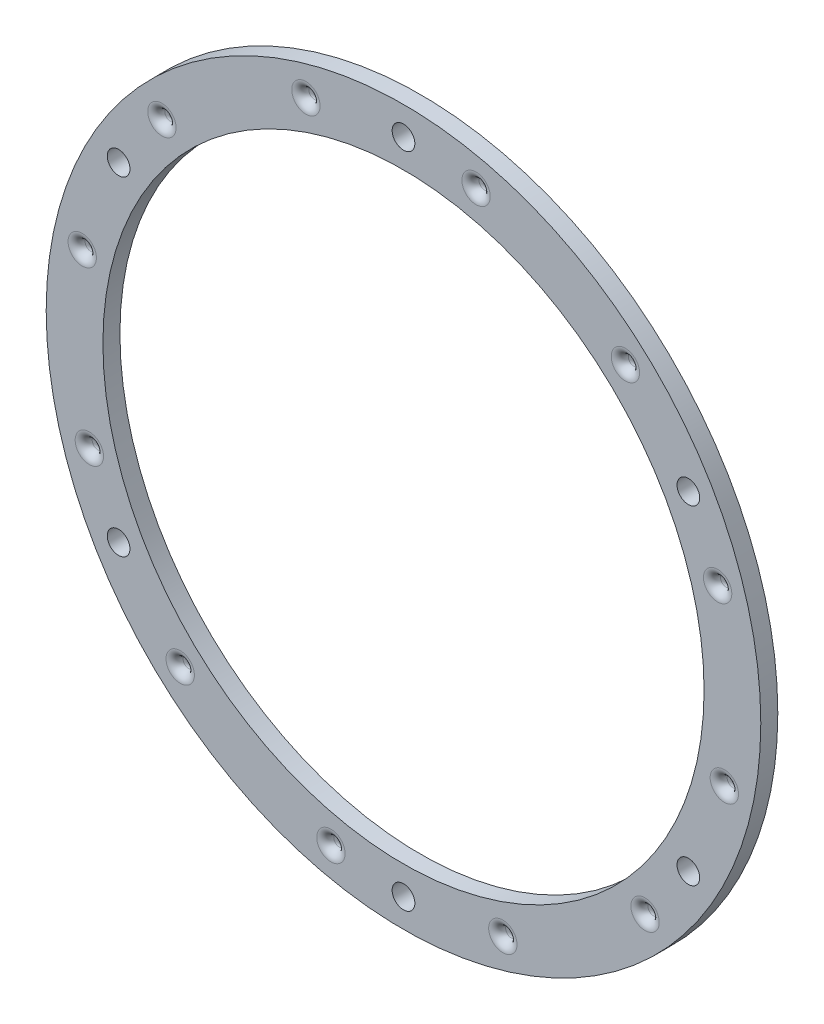
SolidWorks part; units mm, degrees
ref_plane "前视基准面" through (0, 0, 0) normal (0, 0, 1) x (1, 0, 0)
ref_plane "上视基准面" through (0, 0, 0) normal (0, 1, 0) x (1, 0, 0)
ref_plane "右视基准面" through (0, 0, 0) normal (1, 0, 0) x (0, 0, -1)
other "Configuration Table"
sketch "草图1" plane through (0, 0, 0) normal (0, 0, 1) x (1, 0, 0)
  line L0 (92.8146, -27.9977) -> (56.5708, -12.7963) construction
  line L1 (94.3787, 22.1606) -> (55.3899, 17.2035) construction
  line L2 (100.4589, 58) -> (0, 0) construction
  line L3 (70.654, 66.381) -> (39.1279, 42.8136) construction
  line L4 (33.6278, 38.6318) -> (56.5539, 56.0626) construction
  line L5 (27.9977, 92.8146) -> (12.7963, 56.5708) construction
  circle A0 centre (0, 0) radius 63
  circle A1 centre (0, 58) radius 2
  circle A22 centre (0, 0) radius 53
  circle A28 centre (50.2295, 29) radius 2
  circle A34 centre (50.2295, -29) radius 2
  circle A40 centre (0, -58) radius 2
  circle A46 centre (-50.2295, -29) radius 2
  circle A52 centre (-50.2295, 29) radius 2
  circle A58 centre (19.8372, 54.5022) radius 2 [skipped]
  circle A59 centre (37.2817, 44.4306) radius 2 [skipped]
  circle A60 centre (57.1188, 10.0716) radius 2 [skipped]
  circle A61 centre (57.1188, -10.0716) radius 2 [skipped]
  circle A62 centre (37.2817, -44.4306) radius 2 [skipped]
  circle A63 centre (19.8372, -54.5022) radius 2 [skipped]
  circle A64 centre (-19.8372, -54.5022) radius 2 [skipped]
  circle A65 centre (-37.2817, -44.4306) radius 2 [skipped]
  circle A66 centre (-57.1188, -10.0716) radius 2 [skipped]
  circle A67 centre (-57.1188, 10.0716) radius 2 [skipped]
  circle A68 centre (-37.2817, 44.4306) radius 2 [skipped]
  circle A69 centre (-19.8372, 54.5022) radius 2 [skipped]
  circle A70 centre (0, 0) radius 58 construction
  circle A71 centre (55.3899, 17.2035) radius 1
  circle A72 centre (56.5708, -12.7963) radius 1
  circle A73 centre (12.7963, 56.5708) radius 1
  circle A74 centre (39.1279, 42.8136) radius 1
  circle A75 centre (-39.3673, -42.5936) radius 1
  circle A76 centre (-12.7963, -56.5708) radius 1
  circle A77 centre (17.5137, -55.2926) radius 1
  circle A78 centre (42.5936, -39.3673) radius 1
  circle A79 centre (-17.2035, 55.3899) radius 1
  circle A80 centre (-42.5936, 39.3673) radius 1
  circle A81 centre (-56.6416, 12.479) radius 1
  circle A82 centre (-55.3899, -17.2035) radius 1
  point P23 (50.2295, 29)
  point P42 (0, 0)
  point P46 (0, 0)
  point P63 (0, 0)
  point P66 (0, 0)
  dimension "D1" = 126
  dimension "D3" = 4
  dimension "D5" = 106
  dimension "D6" = 18
  dimension "D4" = 2
  dimension "D7" = 2
  dimension "D8" = 2
  dimension "D9" = 2
  dimension "D2" = 58
extrude "凸台-拉伸1" add sketch "草图1" along normal blind 3
fillet "圆角1" radius 1.5 24 edges at (-54.3899, -17.2035, 0) (-55.6416, 12.479, 0) (-41.5936, 39.3673, 0) (-16.2035, 55.3899, 0) (13.7963, 56.5708, 0) (40.1279, 42.8136, 0) (56.3899, 17.2035, 0) (57.5708, -12.7963, 0) (43.5936, -39.3673, 0) (18.5137, -55.2926, 0) (-11.7963, -56.5708, 0) (-38.3673, -42.5936, 0) (13.7963, 56.5708, 3) (40.1279, 42.8136, 3) (56.3899, 17.2035, 3) (57.5708, -12.7963, 3) (43.5936, -39.3673, 3) (18.5137, -55.2926, 3) (-11.7963, -56.5708, 3) (-38.3673, -42.5936, 3) (-54.3899, -17.2035, 3) (-55.6416, 12.479, 3) (-41.5936, 39.3673, 3) (-16.2035, 55.3899, 3)
